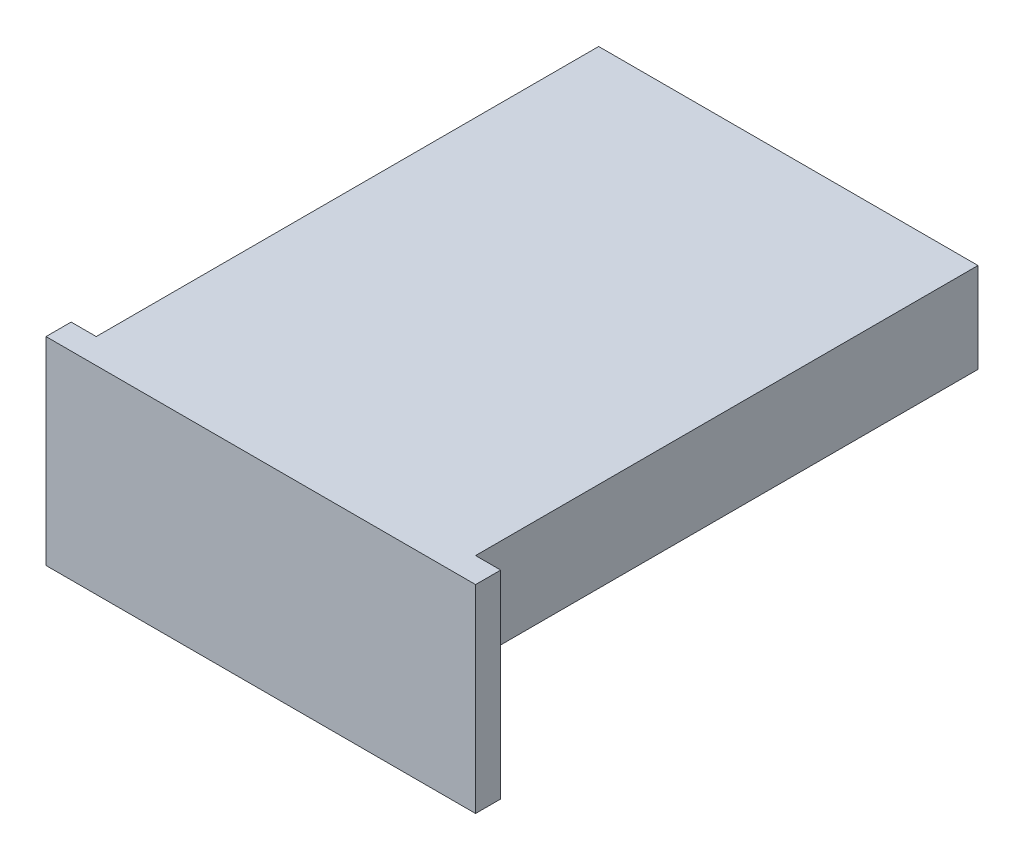
SolidWorks part; units mm, degrees
ref_plane "Front Plane" through (0, 0, 0) normal (0, 0, 1) x (1, 0, 0)
ref_plane "Top Plane" through (0, 0, 0) normal (0, 1, 0) x (1, 0, 0)
ref_plane "Right Plane" through (0, 0, 0) normal (1, 0, 0) x (0, 0, -1)
sketch "Sketch1" plane through (0, -22.4385, -0.0002) normal (0, 1, 0) x (1, 0, 0)
  line L4 (80.038, 6.103) -> (78.038, 6.103)
  line L5 (80.038, 6.103) -> (78.038, 6.103)
  line L6 (78.038, 6.103) -> (78.038, 26.103)
  line L7 (78.038, 6.103) -> (78.038, 26.103)
  line L14 (78.038, 26.103) -> (62.938, 26.103)
  line L15 (78.038, 26.103) -> (62.938, 26.103)
  line L16 (62.938, 26.103) -> (62.938, 6.103)
  line L17 (62.938, 26.103) -> (62.938, 6.103)
  line L26 (146.4404, 26.103) -> (131.338, 26.103)
  line L27 (146.4404, 26.103) -> (131.338, 26.103)
  line L28 (131.338, 26.103) -> (131.338, 6.103)
  line L29 (131.338, 26.103) -> (131.338, 6.103)
  line L75 (131.338, 6.103) -> (129.338, 6.103)
  line L76 (131.338, 6.103) -> (129.338, 6.103)
  line L77 (129.338, 6.103) -> (129.338, 26.103)
  line L78 (129.338, 6.103) -> (129.338, 26.103)
  line L79 (62.938, 6.103) -> (60.5428, 6.103)
  line L80 (62.938, 6.103) -> (60.5428, 6.103)
  line L81 (146.4404, 6.103) -> (146.4404, 26.103)
  line L82 (146.4404, 6.103) -> (146.4404, 26.103)
  line L83 (129.338, 26.103) -> (114.238, 26.103)
  line L84 (129.338, 26.103) -> (114.238, 26.103)
  line L85 (114.238, 26.103) -> (114.238, 6.103)
  line L86 (114.238, 26.103) -> (114.238, 6.103)
  line L87 (114.238, 6.103) -> (112.238, 6.103)
  line L88 (114.238, 6.103) -> (112.238, 6.103)
  line L89 (112.238, 6.103) -> (112.238, 26.103)
  line L90 (112.238, 6.103) -> (112.238, 26.103)
  line L91 (112.238, 26.103) -> (97.138, 26.103)
  line L92 (112.238, 26.103) -> (97.138, 26.103)
  line L93 (97.138, 26.103) -> (97.138, 6.103)
  line L94 (97.138, 26.103) -> (97.138, 6.103)
  line L95 (97.138, 6.103) -> (95.138, 6.103)
  line L96 (97.138, 6.103) -> (95.138, 6.103)
  line L97 (95.138, 6.103) -> (95.138, 26.103)
  line L98 (95.138, 6.103) -> (95.138, 26.103)
  line L99 (95.138, 26.103) -> (80.038, 26.103)
  line L100 (95.138, 26.103) -> (80.038, 26.103)
  line L101 (80.038, 26.103) -> (80.038, 6.103)
  line L102 (80.038, 26.103) -> (80.038, 6.103)
  line L111 (149.0321, 6.103) -> (146.4404, 6.103)
  line L112 (149.0321, 6.103) -> (146.4404, 6.103)
  arc A1 (60.5428, 6.103) -> (60.5959, 6.0115) centre (73.6219, 13.6322) ccw
  arc A2 (60.5428, 6.103) -> (60.5959, 6.0115) centre (73.6219, 13.6322) ccw
  spline S3 degree 3 poles (1817.8665, 957.8692) (-1812.7007, -801.1687) (1972.7377, 742.4675) (-1779.9076, -773.9188) knots -29.662381 -29.662381 -29.662381 -29.662381 32.998383 32.998383 32.998383 32.998383 only from (61.1644, 5.1151) to (62.5644, 3.3076)
  spline S4 degree 3 poles (548.8295, -1936.4915) (68.1721, 117.1489) (41.7438, 23.7507) (63.9834, 1.8165) (64.3645, 1.4758) (65.5511, 0.508) (66.3975, -0.0681) (68.1618, -1.131) (69.0656, -1.6129) (70.9072, -2.4757) (71.8473, -2.8546) (73.758, -3.5302) (74.728, -3.8283) (76.6807, -4.3902) (77.6629, -4.6553) (79.6355, -5.163) (80.6269, -5.4019) (82.6154, -5.8388) (83.6137, -6.0359) (85.6141, -6.4083) (86.6163, -6.584) (88.622, -6.928) (89.6256, -7.0959) (92.6392, -7.5851) (94.6533, -7.8906) (97.6787, -8.2804) (98.6882, -8.3974) (100.712, -8.5681) (101.7263, -8.6231) (103.759, -8.6779) (104.7772, -8.6815) (106.8164, -8.6518) (107.8346, -8.6197) (109.8636, -8.4895) (110.8742, -8.3881) (112.8914, -8.1479) (113.898, -8.0094) (116.9153, -7.5695) (118.9237, -7.2381) (121.9279, -6.7189) (122.9282, -6.542) (124.9259, -6.1777) (125.9229, -5.9891) (127.9067, -5.5749) (128.8931, -5.3485) (130.8559, -4.8592) (131.8333, -4.6003) (133.7815, -4.0591) (134.7528, -3.7785) (136.6775, -3.1531) (137.6304, -2.8065) (139.0374, -2.2069) (139.5031, -1.9951) (140.4295, -1.554) (140.891, -1.3271) (141.8041, -0.8385) (142.2585, -0.5733) (143.1225, 0.0059) (143.536, 0.3177) (144.1477, 0.7954) (144.3502, 0.9564) (144.7554, 1.2781) (144.9578, 1.4391) (162.9576, 16.0958) (166.0883, 48.1369) (-1083.6442, 1578.9651) knots -0.820445 -0.820445 -0.820445 -0.820445 0.115071 0.115071 0.130696 0.130696 0.161946 0.161946 0.193196 0.193196 0.224446 0.224446 0.255696 0.255696 0.286946 0.286946 0.318196 0.318196 0.349446 0.349446 0.380696 0.380696 0.411946 0.411946 0.474446 0.474446 0.505696 0.505696 0.536946 0.536946 0.568196 0.568196 0.599446 0.599446 0.630696 0.630696 0.661946 0.661946 0.724446 0.724446 0.755696 0.755696 0.786946 0.786946 0.818196 0.818196 0.849446 0.849446 0.880696 0.880696 0.911946 0.911946 0.927571 0.927571 0.943196 0.943196 0.958821 0.958821 0.974446 0.974446 0.982259 0.982259 0.990071 0.990071 1.683487 1.683487 1.683487 1.683487 only from (62.5644, 3.3076) to (145.9103, 2.2401)
  spline S6 degree 3 poles (61.1644, 5.1151) (61.5972, 4.4806) (62.0704, 3.8809) (62.5644, 3.3076) knots 0 0 0 0 0.685452 0.685452 0.685452 0.685452 construction
  spline S7 degree 3 poles (62.5644, 3.3076) (62.9009, 2.9175) (63.2527, 2.5372) (63.9834, 1.8165) (64.3645, 1.4758) (65.5511, 0.508) (66.3975, -0.0681) (68.1618, -1.131) (69.0656, -1.6129) (70.9072, -2.4757) (71.8473, -2.8546) (73.758, -3.5302) (74.728, -3.8283) (76.6807, -4.3902) (77.6629, -4.6553) (79.6355, -5.163) (80.6269, -5.4019) (82.6154, -5.8388) (83.6137, -6.0359) (85.6141, -6.4083) (86.6163, -6.584) (88.622, -6.928) (89.6256, -7.0959) (92.6392, -7.5851) (94.6533, -7.8906) (97.6787, -8.2804) (98.6882, -8.3974) (100.712, -8.5681) (101.7263, -8.6231) (103.759, -8.6779) (104.7772, -8.6815) (106.8164, -8.6518) (107.8346, -8.6197) (109.8636, -8.4895) (110.8742, -8.3881) (112.8914, -8.1479) (113.898, -8.0094) (116.9153, -7.5695) (118.9237, -7.2381) (121.9279, -6.7189) (122.9282, -6.542) (124.9259, -6.1777) (125.9229, -5.9891) (127.9067, -5.5749) (128.8931, -5.3485) (130.8559, -4.8592) (131.8333, -4.6003) (133.7815, -4.0591) (134.7528, -3.7785) (136.6775, -3.1531) (137.6304, -2.8065) (139.0374, -2.2069) (139.5031, -1.9951) (140.4295, -1.554) (140.891, -1.3271) (141.8041, -0.8385) (142.2585, -0.5733) (143.1225, 0.0059) (143.536, 0.3177) (144.1477, 0.7954) (144.3502, 0.9564) (144.7554, 1.2781) (144.9578, 1.4391) (145.4132, 1.8099) (145.6651, 2.021) (145.9103, 2.2401) knots 0.099446 0.099446 0.099446 0.099446 0.115071 0.115071 0.130696 0.130696 0.161946 0.161946 0.193196 0.193196 0.224446 0.224446 0.255696 0.255696 0.286946 0.286946 0.318196 0.318196 0.349446 0.349446 0.380696 0.380696 0.411946 0.411946 0.474446 0.474446 0.505696 0.505696 0.536946 0.536946 0.568196 0.568196 0.599446 0.599446 0.630696 0.630696 0.661946 0.661946 0.724446 0.724446 0.755696 0.755696 0.786946 0.786946 0.818196 0.818196 0.849446 0.849446 0.880696 0.880696 0.911946 0.911946 0.927571 0.927571 0.943196 0.943196 0.958821 0.958821 0.974446 0.974446 0.982259 0.982259 0.990071 0.990071 1 1 1 1 construction
  spline S16 degree 3 poles (1372.6595, -1576.7465) (65.1848, 24.8122) (129.0525, -14.1517) (146.6971, 2.9872) (147.0468, 3.3764) (147.7131, 4.1895) (148.0276, 4.6072) (165.4719, 29.2726) (129.935, 85.2105) (-1517.3371, 1110.9512) knots -0.67008 -0.67008 -0.67008 -0.67008 0.055384 0.055384 0.071009 0.071009 0.086634 0.086634 0.976126 0.976126 0.976126 0.976126 only from (145.9103, 2.2401) to (149.0321, 6.103)
  spline S17 degree 3 poles (145.9103, 2.2401) (146.0509, 2.3658) (146.1894, 2.4941) (146.6971, 2.9872) (147.0468, 3.3764) (147.7131, 4.1895) (148.0276, 4.6072) (148.5757, 5.3822) (148.8117, 5.7379) (149.0321, 6.103) knots 0.049688 0.049688 0.049688 0.049688 0.055384 0.055384 0.071009 0.071009 0.086634 0.086634 0.099446 0.099446 0.099446 0.099446
  spline S46 degree 3 poles (1817.9148, 957.8926) (-1812.905, -801.2651) (1973.1102, 742.6193) (-1780.4368, -774.1326) knots -28.662659 -28.662659 -28.662659 -28.662659 34.001328 34.001328 34.001328 34.001328 only from (60.5959, 6.0115) to (61.1644, 5.1151)
  spline S47 degree 3 poles (60.5959, 6.0115) (60.7756, 5.7048) (60.9657, 5.4063) (61.1644, 5.1151) knots 0.685452 0.685452 0.685452 0.685452 1 1 1 1
  dimension "D1" = 0
sketch "Sketch3" plane through (0, 0.0002, -26.103) normal (0, 0, 1) x (1, 0, 0)
  line L1 (97.138, 49.3018) -> (112.238, 49.3018)
  line L2 (97.138, 49.3018) -> (97.138, 45.7197)
  line L3 (97.138, 45.7197) -> (112.238, 45.7197)
  line L4 (112.238, 49.3018) -> (112.238, 45.7197)
  line L6 (97.1381, 145.3715) -> (97.138, -22.4385) construction
  line L7 (112.2381, 145.3715) -> (112.238, -22.4385) construction
  dimension "D1" = 15.1
extrude "Boss-Extrude1" add sketch "Sketch3" along normal up to surface (20 mm away)
sketch "Sketch4" plane through (0, 0, -6.103) normal (0, 0, 1) x (1, 0, 0)
  line L1 (96.138, 49.3018) -> (113.238, 49.3018)
  line L2 (96.138, 49.3018) -> (96.138, 41.4088)
  line L3 (96.138, 41.4088) -> (113.238, 41.4088)
  line L4 (113.238, 49.3018) -> (113.238, 41.4088)
  line L5 (97.138, 49.3018) -> (112.238, 49.3018) construction
  line L6 (95.138, 37.5077) -> (97.138, 37.5077) construction
  line L7 (95.1381, 145.3715) -> (95.138, -22.4385) construction
  line L8 (97.1381, 145.3715) -> (97.138, -22.4385) construction
  line L9 (96.138, 37.5077) -> (96.138, 51.6023) construction
  line L10 (112.238, 37.5077) -> (114.238, 37.5077) construction
  line L11 (112.2381, 145.3715) -> (112.238, -22.4385) construction
  line L12 (114.2381, 145.3715) -> (114.238, -22.4385) construction
  line L13 (113.238, 37.5077) -> (113.238, 51.6023) construction
extrude "Boss-Extrude2" add sketch "Sketch4" along normal blind 1
